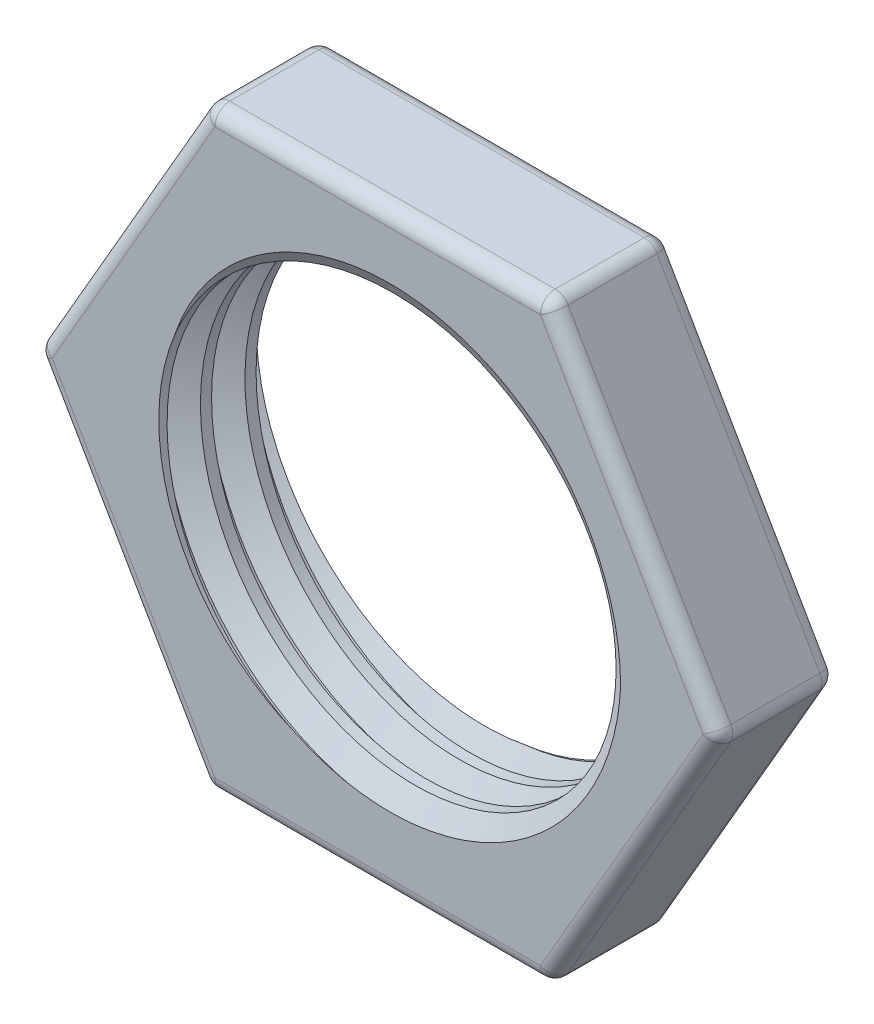
SolidWorks part; units mm, degrees
ref_plane "Ebene vorne" through (0, 0, 0) normal (0, 0, 1) x (1, 0, 0)
ref_plane "Ebene oben" through (0, 0, 0) normal (0, 1, 0) x (1, 0, 0)
ref_plane "Ebene rechts" through (0, 0, 0) normal (1, 0, 0) x (0, 0, -1)
sketch "Skizze1" plane through (0, 0, 0) normal (0, 0, 1) x (1, 0, 0)
  line L1 (-11.547, 0) -> (-5.7735, -10)
  line L2 (-5.7735, -10) -> (5.7735, -10)
  line L3 (5.7735, -10) -> (11.547, 0)
  line L4 (11.547, 0) -> (5.7735, 10)
  line L5 (5.7735, 10) -> (-5.7735, 10)
  line L6 (-5.7735, 10) -> (-11.547, 0)
  circle A0 centre (0, 0) radius 10 construction
  circle A1 centre (0, 0) radius 8.188
  dimension "D1" = 20
  dimension "D2" = 16.376
extrude "Aufsatz-Linear austragen1" add sketch "Skizze1" along normal blind 4
thread "Gewinde1" pitch 1.5 method extrude profile "Gewindeprofil1" start angle 0, offset 2, length 0, pitch 1.5, diameter 16.376
ref_plane "Ebene1" through (8.188, 0, -2) normal (0, -1, 0) x (1, 0, 0)
sketch "Gewindeprofil1" plane through (8.188, 0, -2) normal (0, -1, 0) x (1, 0, 0)
  line L0 (0, 0) -> (0, 1.5) construction
  line L11 (0, 0) -> (0, 1.3125)
  line L12 (0, 1.3125) -> (-0.8119, 0.8437)
  line L13 (-0.8119, 0.8437) -> (-0.8119, 0.4687)
  line L15 (-0.8119, 0.4687) -> (0, 0)
  line L17 (-0.8119, 0.6562) -> (0, 0.6562) construction
  point P2 (0, 0)
  dimension "Pitch" = 1.5
  dimension "Profile_Angle" = 60
  dimension "Profile_Land" = 0.375
  dimension "Profile_Height" = 0.8119
sketch "Skizze7" plane through (-8.6603, 5, 0) normal (-0.866, 0.5, 0) x (0, 0, 1)
  line L0 (4, -8.188) -> (4, 8.188) construction
  line L1 (0, -9.9453) -> (-5.2804, -9.9453)
  line L2 (0, -9.9453) -> (0, 11.1154)
  line L3 (0, 11.1154) -> (-5.2804, 11.1154)
  line L4 (-5.2804, -9.9453) -> (-5.2804, 11.1154)
  line L5 (4, -11.1711) -> (9.8187, -11.1711)
  line L6 (4, -11.1711) -> (4, 10.7254)
  line L7 (4, 10.7254) -> (9.8187, 10.7254)
  line L8 (9.8187, -11.1711) -> (9.8187, 10.7254)
  line L9 (0, -5.7735) -> (0, -11.547) construction
  line L10 (4, -5.7735) -> (4, -11.547) construction
extrude "Schnitt-Linear austragen1" cut sketch "Skizze7" against normal through all
fillet "Verrundung1" radius 0.5 18 edges at (8.6603, -5, 4) (8.6603, -5, 0) (0, -10, 4) (5.7735, -10, 2) (0, -10, 0) (-8.6603, -5, 4) (-5.7735, -10, 2) (-8.6603, -5, 0) (-8.6603, 5, 4) (-11.547, 0, 2) (-8.6603, 5, 0) (0, 10, 4) (-5.7735, 10, 2) (0, 10, 0) (11.547, 0, 2) (8.6603, 5, 4) (5.7735, 10, 2) (8.6603, 5, 0)
